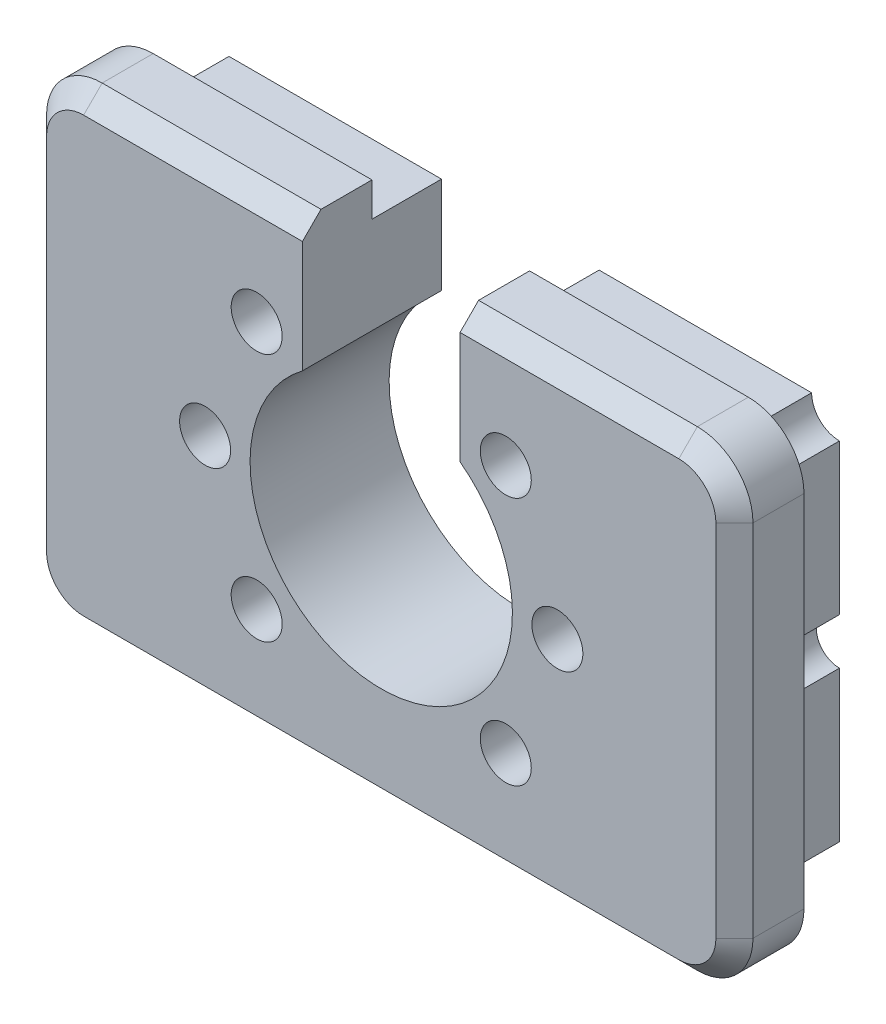
SolidWorks part; units mm, degrees
material "PET"
ref_plane "Front Plane" through (0, 0, 0) normal (0, 0, 1) x (1, 0, 0)
ref_plane "Top Plane" through (0, 0, 0) normal (0, 1, 0) x (1, 0, 0)
ref_plane "Right Plane" through (0, 0, 0) normal (1, 0, 0) x (0, 0, -1)
sketch "Sketch1" plane through (0, 0, 0) normal (0, 0, 1) x (1, 0, 0)
  line L1 (38.1, -25.4) -> (-38.1, -25.4)
  line L2 (38.1, -25.4) -> (38.1, 25.4)
  line L3 (38.1, 25.4) -> (-38.1, 25.4)
  line L4 (-38.1, -25.4) -> (-38.1, 25.4)
  line L5 (38.1, -25.4) -> (-38.1, 25.4) construction
  line L6 (38.1, 25.4) -> (-38.1, -25.4) construction
  point P0 (0, 0)
  dimension "D1" = 50.8
  dimension "D2" = 76.2
extrude "Boss-Extrude1" add sketch "Sketch1" against normal blind 7.5
sketch "Sketch2" plane through (0, 0, -7.5) normal (0, 0, -1) x (-1, 0, 0)
  line L8 (34.425, -21.725) -> (34.425, 21.725)
  line L9 (34.425, 21.725) -> (-34.425, 21.725)
  line L10 (-34.425, 21.725) -> (-34.425, -21.725)
  line L11 (-34.425, -21.725) -> (34.425, -21.725)
  line L12 (34.425, -21.725) -> (34.425, 21.725)
  line L13 (34.425, 21.725) -> (-34.425, 21.725)
  line L14 (-34.425, 21.725) -> (-34.425, -21.725)
  line L15 (-34.425, -21.725) -> (34.425, -21.725)
  dimension "D1" = 3.675
extrude "Boss-Extrude2" add sketch "Sketch2" along normal blind 7.5
sketch "Sketch3" plane through (0, 0, 0) normal (0, 0, 1) x (1, 0, 0)
  line L0 (0, 0) -> (0, 51.1675) construction
  line L1 (38.1, 25.4) -> (-38.1, 25.4) construction
  line L2 (8.5, 11.3125) -> (-8.5, 11.3125) construction
  line L3 (8.5, 11.3125) -> (8.5, 25.4)
  line L4 (8.5, 25.4) -> (-8.5, 25.4)
  line L5 (-8.5, 11.3125) -> (-8.5, 25.4)
  line L6 (8.5, 11.3125) -> (-8.5, 25.4) construction
  line L7 (8.5, 25.4) -> (-8.5, 11.3125) construction
  line L8 (0, 0) -> (-19, 0) construction
  arc A0 (-8.5, 11.3125) -> (8.5, 11.3125) centre (0, 0) ccw
  circle A1 centre (-19, 0) radius 2.75
  circle A2 centre (-13.435, 13.435) radius 2.75
  circle A3 centre (0, 19) radius 2.75 construction
  circle A4 centre (13.435, 13.435) radius 2.75
  circle A5 centre (19, 0) radius 2.75
  circle A6 centre (13.435, -13.435) radius 2.75
  circle A7 centre (0, -19) radius 2.75 construction
  circle A8 centre (-13.435, -13.435) radius 2.75
  point P3 (0, 18.3562)
  point P28 (0, 0)
  dimension "D1" = 28.3
  dimension "D4" = 5.5
  dimension "D2" = 17
  dimension "D3" = 19
  dimension "D5" = 8
extrude "Cut-Extrude1" cut sketch "Sketch3" against normal through all
fillet "Fillet1" radius 6 4 edges at (38.1, -25.4, -3.75) (-38.1, -25.4, -3.75) (-38.1, 25.4, -3.75) (38.1, 25.4, -3.75)
sketch "Sketch4" plane through (0, 0, -15) normal (0, 0, -1) x (-1, 0, 0)
  line L0 (-34.425, 21.725) -> (-34.425, -21.725) construction
  line L5 (-34.425, -21.725) -> (0, -21.725) construction
  line L6 (0, 0) -> (0, -21.725) construction
  circle A0 centre (-34.425, 21.725) radius 3
  circle A1 centre (-34.425, -21.725) radius 3
  circle A2 centre (-34.425, 0) radius 2.5
  circle A3 centre (0, -21.725) radius 2.5
  circle A4 centre (34.425, -21.725) radius 3
  circle A5 centre (34.425, 0) radius 2.5
  circle A6 centre (34.425, 21.725) radius 3
  arc A7 (-32.1, 25.4) -> (-38.1, 19.4) centre (-32.1, 19.4) ccw construction
  arc A8 (-32.1, 25.4) -> (-38.1, 19.4) centre (-32.1, 19.4) ccw construction
  dimension "D4" = 5
  dimension "D5" = 6
  dimension "D1" = 6
extrude "Cut-Extrude2" cut sketch "Sketch4" against normal up to surface (7.5 mm away) up to face at (0, 5.8906, -7.5)
chamfer "Chamfer1" distance 2 angle 45 9 edges at (-20.3, 25.4, 0) (-36.3426, 23.6426, 0) (-38.1, 0, 0) (-36.3426, -23.6426, 0) (0, -25.4, 0) (36.3426, -23.6426, 0) (38.1, 0, 0) (36.3426, 23.6426, 0) (20.3, 25.4, 0)
chamfer "Chamfer2" [suppressed] distance 3 angle 45
equation "\"hole_radius\"= 14.15mm"
equation "\"D1@Sketch3\"=\"hole_radius\"*2"
equation "\"M5_tap\"=4.2mm       ' Below you can do mesurements as follows: cm, mm, ft, in, m, "
equation "\"M5_clearence\"=5.5mm"
equation "\"M6_tap\"=5mm"
equation "\"M6_clearence\"=6.6mm"
equation "\"work_area_width\"=1100mm"
equation "\"work_area_depth\"=900mm"
equation "\"steel_base_width\"=3in "
equation "\"steel_base_height\"=2in"
equation "\"steel_base_wall_thickness\"=0.125in"
equation "\"steel_base_radius\"=6mm"
equation "\"steel_sides_width\"=3in     'this tube is rotated so flip width/height"
equation "\"steel_sides_height\"=2in    'this tube is rotated so flip width/height"
equation "\"steel_sides_wall_thickness\"=0.125in"
equation "\"steel_sides_radius\"=6mm"
equation "\"steel_gantry_width\"=4in    'this tube is rotated so flip width/height"
equation "\"steel_gantry_height\"=3in    'this tube is rotated so flip width/height"
equation "\"steel_gantry_wall_thickness\"=0.125in"
equation "\"steel_gantry_radius\"=6mm"
equation "\"steel_rollers_width\"=3in"
equation "\"steel_rollers_height\"=2in    'keep as low as possible as this increases how big plastic parts are"
equation "\"steel_rollers_wall_thickness\"=0.125in"
equation "\"steel_rollers_radius\"=6mm"
equation "\"steel_zbox_width\"=4in     'if the gantry height (rotated) is too thick, a wider zbox is necessary"
equation "\"steel_zbox_height\"=2in     'hole patteren changes as the zbox and gantry height (rotated) changes."
equation "\"steel_zbox_wall_thickness\"=0.125in"
equation "\"steel_zbox_radius\"=6mm"
equation "\"D2@Sketch1\"=\"steel_rollers_width\""
equation "\"D1@Sketch1\"=\"steel_rollers_height\""
equation "\"D1@Sketch2\"=\"steel_rollers_wall_thickness\" + 0.5mm"
equation "\"D5@Sketch4\"=\"D1@Sketch4\""
